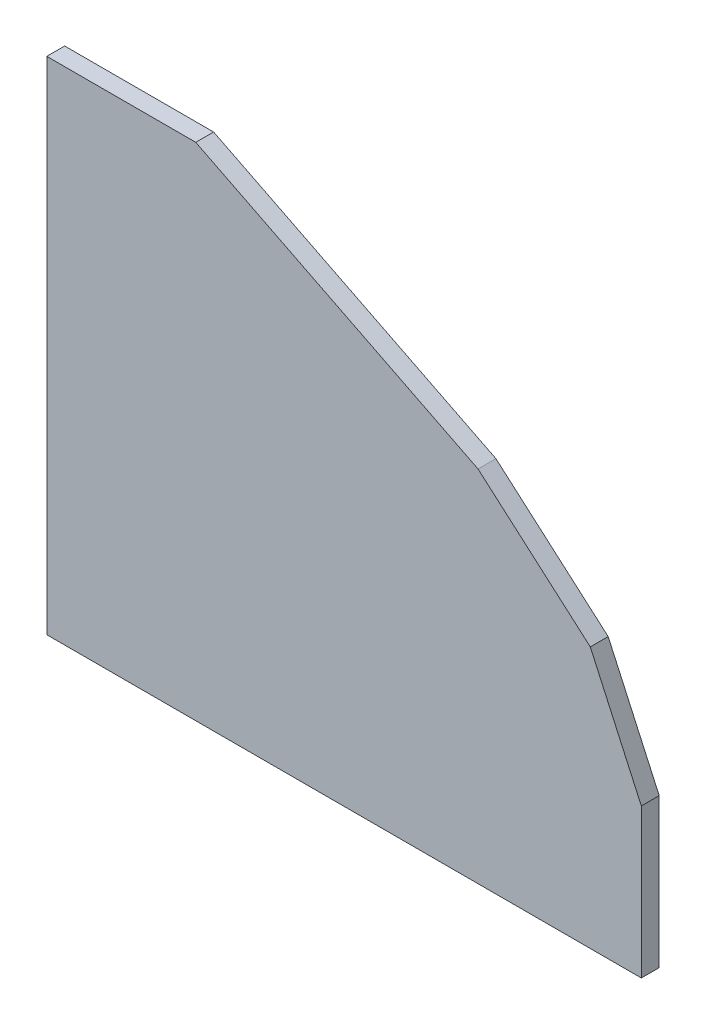
SolidWorks part; units mm, degrees
material "AISI 1020"
ref_plane "Спереди" through (0, 0, 0) normal (0, 0, 1) x (1, 0, 0)
ref_plane "Сверху" through (0, 0, 0) normal (0, 1, 0) x (1, 0, 0)
ref_plane "Справа" through (0, 0, 0) normal (1, 0, 0) x (0, 0, -1)
sketch "Эскиз1" plane through (0, 0, 0) normal (0, 0, 1) x (1, 0, 0)
  line L0 (249.5384, 50) -> (50, 50)
  line L3 (50, 50) -> (50, 218.1198)
  line L4 (50, 218.1198) -> (100, 218.1198)
  line L5 (100, 218.1198) -> (194.7382, 170.5476)
  line L6 (2192.4797, 2460) -> (133.1795, 100) construction
  line L7 (194.7382, 170.5476) -> (232.4121, 137.6739)
  line L8 (2258.8386, 2460) -> (199.5384, 100) construction
  line L9 (232.4121, 137.6739) -> (249.5384, 100)
  line L11 (100, 5060) -> (100, 0) construction
  line L12 (249.5384, 100) -> (249.5384, 50)
  line L13 (232.4121, 137.6739) -> (199.5384, 100) construction
  line L14 (4484.0362, 100) -> (100, 100) construction
  line L15 (199.5384, 100) -> (249.5384, 100) construction
  line L16 (100, 218.1198) -> (100, 100) construction
  line L17 (100, 100) -> (194.7382, 170.5476) construction
  line L18 (0, 100) -> (0, 2460) construction
  line L19 (4498.9012, 0) -> (100, 0) construction
  dimension "D1" = 50
  dimension "D2" = 50
  dimension "D3" = 50
base flange "Базовая кромка1" sketch "Эскиз1" thickness 6 reverse thickness direction no parameters "D1"=0.75
sketch "Сгиб-Линии1" plane through (0, 0, 0) normal (0, 1, 0) x (1, 0, 0)
sketch "Граничная рамка1" plane through (0, 0, 0) normal (0, 1, 0) x (1, 0, 0)
sheet metal parameters "Листовой металл3" thickness 6 parameters "D1"=0.75
flat pattern "Развертка3" [suppressed]
sketch "Сгиб-Линии2" plane through (0, 0, 0) normal (0, 1, 0) x (1, 0, 0)
sketch "Граничная рамка2" [suppressed] plane through (0, 0, 0) normal (0, 1, 0) x (1, 0, 0)
